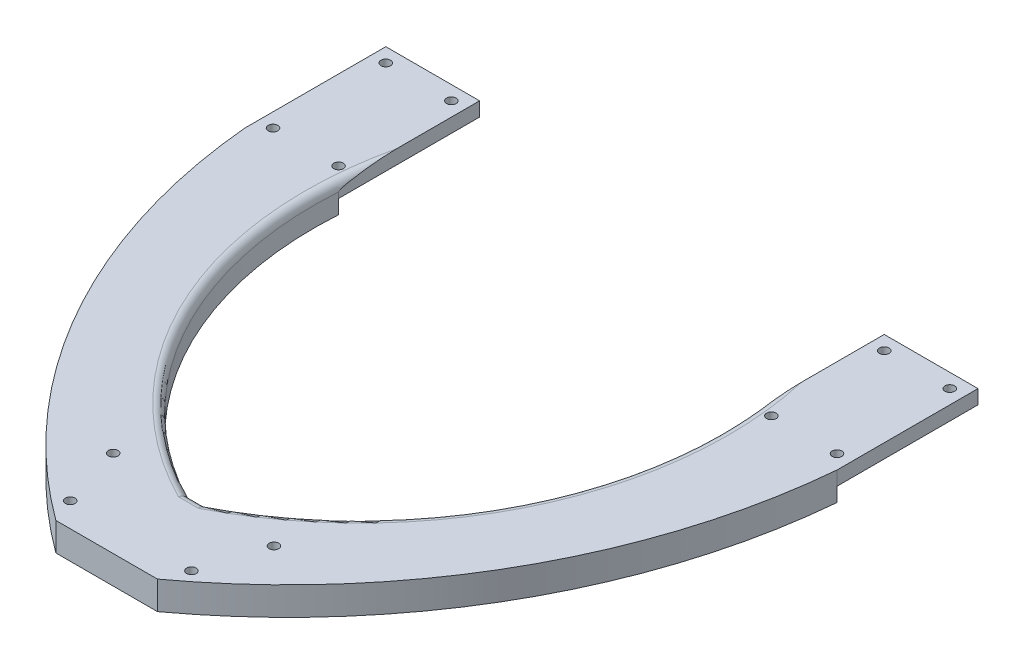
SolidWorks part; units mm, degrees
ref_plane "Ebene vorne" through (0, 0, 0) normal (0, 0, 1) x (1, 0, 0)
ref_plane "Ebene oben" through (0, 0, 0) normal (0, 1, 0) x (1, 0, 0)
ref_plane "Ebene rechts" through (0, 0, 0) normal (1, 0, 0) x (0, 0, -1)
sketch "Skizze1" plane through (0, 0, 0) normal (0, 1, 0) x (1, 0, 0)
  line L1 (-105, -210) -> (105, -210)
  line L2 (-105, -210) -> (-105, 210)
  line L3 (-105, 210) -> (105, 210)
  line L4 (105, -210) -> (105, 210)
  line L5 (-105, -210) -> (105, 210) construction
  line L6 (-105, 210) -> (105, -210) construction
  point P0 (0, 0)
  dimension "D1" = 210
  dimension "D2" = 420
extrude "Aufsatz-Linear austragen1" add sketch "Skizze1" along normal blind 10
ref_plane "Ebene1" through (0, -97.5366, 81.8429) normal (0, -0.766, 0.6428) x (1, 0, 0)
sketch "Skizze2" plane through (0, -97.5366, 81.8429) normal (0, -0.766, 0.6428) x (1, 0, 0)
  line L1 (-105, 167.2972) -> (105, 167.2972) construction
  circle A0 centre (0, 147.2972) radius 5
  dimension "D1" = 10
  dimension "D2" = 20
extrude "Schnitt-Linear austragen1" [suppressed] cut sketch "Skizze2" against normal blind 30 and the other way blind 10
sketch "Skizze3" [suppressed] plane through (0, -67.9923, 57.0523) normal (0, -0.766, 0.6428) x (1, 0, 0)
  circle A0 centre (0, 101.3345) radius 5
  dimension "D1" = 10
extrude "Aufsatz-Linear austragen2" [suppressed] add sketch "Skizze3" along normal blind 0.1
sketch "Skizze4" plane through (0, -97.5366, 81.8429) normal (0, -0.766, 0.6428) x (1, 0, 0)
  line L0 (0, 167.2972) -> (0, 159.9002) construction
  line L1 (-105, 167.2972) -> (105, 167.2972) construction
  line L2 (-25, 167.2972) -> (-25, 202.2972)
  line L3 (-25, 202.2972) -> (25, 202.2972)
  line L4 (-25, 167.2972) -> (25, 167.2972)
  line L5 (25, 167.2972) -> (25, 202.2972)
  point P10 (0, 202.2972)
  dimension "D1" = 50
  dimension "D2" = 35
extrude "Aufsatz-Linear austragen3" [suppressed] add sketch "Skizze4" against normal blind 10 separate body
sketch "Skizze5" plane through (0, 10, 0) normal (0, 1, 0) x (1, 0, 0)
  line L0 (0, 0) -> (0, -210) construction
  line L1 (-105, -210) -> (105, -210) construction
  line L2 (105, -210) -> (18, -210)
  line L3 (-18, -210) -> (-105, -56)
  line L4 (-105, 210) -> (-105, -210) construction
  line L5 (-105, -56) -> (-105, -210)
  line L6 (-105, -210) -> (-18, -210)
  line L7 (105, -56) -> (105, -210)
  line L8 (18, -210) -> (105, -56)
  line L9 (-105, 210) -> (-105, 125)
  line L10 (-105, 125) -> (105, 125)
  line L11 (105, -210) -> (105, 210) construction
  line L12 (105, 125) -> (105, 210)
  line L13 (105, 210) -> (-105, 210)
  line L14 (71.7468, -56) -> (-71.7468, -56)
  line L15 (-71.7468, -56) -> (-2.8247, -178)
  line L16 (71.7468, -56) -> (2.8247, -178)
  line L17 (-2.8247, -178) -> (2.8247, -178)
  line L18 (2.8247, -178) -> (0, -183) construction
  line L19 (-2.8247, -178) -> (0, -183) construction
  point P27 (0, -56)
  dimension "D1" = 36
  dimension "D2" = 154
  dimension "D3" = 85
  dimension "D4" = 32
  dimension "D5" = 27
extrude "Schnitt-Linear austragen2" cut sketch "Skizze5" against normal blind 10
sketch "Skizze6" plane through (0, 10, 0) normal (0, 1, 0) x (1, 0, 0)
  line L0 (0, -210) -> (0, -178) construction
  line L1 (-18, -210) -> (18, -210) construction
  line L2 (-2.8247, -178) -> (2.8247, -178) construction
  line L3 (0, -196.59) -> (-21.075, -196.59) construction
  circle A0 centre (-11, -205) radius 1.7
  circle A1 centre (-11, -188.18) radius 1.7
  circle A2 centre (11, -205) radius 1.7
  circle A3 centre (11, -188.18) radius 1.7
  dimension "D1" = 3.4
  dimension "D2" = 11
  dimension "D3" = 5
  dimension "D4" = 13.41
extrude "Schnitt-Linear austragen3" [suppressed] cut sketch "Skizze6" against normal through all
sketch "Skizze7" [suppressed] plane through (0, 0, 0) normal (0, -1, 0) x (1, 0, 0)
  line L0 (-11, 205) -> (-11, 210) construction
  line L1 (-18, 210) -> (18, 210) construction
  line L2 (-11, 205) -> (-5.1092, 205) construction
  line L3 (-11, 208.4064) -> (-8.05, 206.7032)
  line L4 (-8.05, 206.7032) -> (-8.05, 203.2968)
  line L5 (-11, 201.5936) -> (-8.05, 203.2968)
  line L6 (-11, 201.5936) -> (-13.95, 203.2968)
  line L7 (-13.95, 206.7032) -> (-13.95, 203.2968)
  line L8 (-11, 208.4064) -> (-13.95, 206.7032)
  line L9 (0, 210) -> (0, 121.6034) construction
  line L10 (11, 205) -> (11, 188.18) construction
  line L11 (11, 196.59) -> (0, 196.59) construction
  line L12 (11, 208.4064) -> (8.05, 206.7032)
  line L13 (11, 201.5936) -> (8.05, 203.2968)
  line L14 (8.05, 206.7032) -> (8.05, 203.2968)
  line L15 (11, 201.5936) -> (13.95, 203.2968)
  line L16 (13.95, 206.7032) -> (13.95, 203.2968)
  line L17 (11, 208.4064) -> (13.95, 206.7032)
  line L18 (-8.05, 186.4768) -> (-8.05, 189.8832)
  line L19 (-11, 191.5864) -> (-13.95, 189.8832)
  line L20 (-11, 191.5864) -> (-8.05, 189.8832)
  line L21 (-13.95, 186.4768) -> (-13.95, 189.8832)
  line L22 (-11, 184.7736) -> (-13.95, 186.4768)
  line L23 (-11, 184.7736) -> (-8.05, 186.4768)
  line L24 (8.05, 186.4768) -> (8.05, 189.8832)
  line L25 (11, 191.5864) -> (8.05, 189.8832)
  line L26 (11, 191.5864) -> (13.95, 189.8832)
  line L27 (13.95, 186.4768) -> (13.95, 189.8832)
  line L28 (11, 184.7736) -> (13.95, 186.4768)
  line L29 (11, 184.7736) -> (8.05, 186.4768)
  point P10 (-8.05, 205)
  dimension "D1" = 120
  dimension "D2" = 5.9
extrude "Schnitt-Linear austragen4" [suppressed] cut sketch "Skizze7" against normal blind 4
sketch "Skizze8" plane through (0, 10, 0) normal (0, 1, 0) x (1, 0, 0)
  line L0 (105, 115.41) -> (78.872, 115.41) construction
  line L1 (105, -56) -> (105, 125) construction
  line L2 (-105, 125) -> (105, 125) construction
  dimension "D1" = 9.59
ref_plane "Ebene2" through (0, 62.6966, -52.6087) normal (0, 0.766, -0.6428) x (-1, 0, 0)
sketch "Skizze9" plane through (0, 62.6966, -52.6087) normal (0, 0.766, -0.6428) x (-1, 0, 0)
  line L0 (-105, -81.9813) -> (-78.872, -81.9813) construction
  line L1 (-105, 49.3264) -> (-105, -89.3277) construction
  line L2 (0, -45.2589) -> (0, -16.2619) construction
  circle A0 centre (-100, -81.9813) radius 1.7
  circle A1 centre (100, -81.9813) radius 1.7
  circle A2 centre (-30, -81.9813) radius 1.7
  circle A3 centre (30, -81.9813) radius 1.7
  dimension "D1" = 3.4
  dimension "D2" = 5
  dimension "D3" = 30
extrude "Schnitt-Linear austragen5" [suppressed] cut sketch "Skizze9" against normal through all and the other way through all
ref_plane "Ebene3" through (0, 55.0361, -46.1808) normal (0, 0.766, -0.6428) x (-1, 0, 0)
sketch "Skizze10" [suppressed] plane through (0, 55.0361, -46.1808) normal (0, 0.766, -0.6428) x (-1, 0, 0)
  line L0 (-95, -81.9813) -> (-100, -81.9813) construction
  line L1 (-95, -81.9813) -> (-95, -30.0694) construction
  line L2 (-95, -78.7482) -> (-97.8, -80.3647)
  line L3 (-97.8, -80.3647) -> (-97.8, -83.5979)
  line L4 (-95, -85.2145) -> (-97.8, -83.5979)
  line L5 (-95, -85.2145) -> (-92.2, -83.5979)
  line L6 (-92.2, -80.3647) -> (-92.2, -83.5979)
  line L7 (-95, -78.7482) -> (-92.2, -80.3647)
  line L8 (0, 0) -> (0, -45.6283) construction
  line L9 (-30, -81.9813) -> (-95, -81.9813) construction
  line L10 (-62.5, -81.9813) -> (-62.5, -23.1343) construction
  line L11 (-32.8, -80.3647) -> (-32.8, -83.5979)
  line L12 (-30, -85.2145) -> (-32.8, -83.5979)
  line L13 (-30, -85.2145) -> (-27.2, -83.5979)
  line L14 (-27.2, -80.3647) -> (-27.2, -83.5979)
  line L15 (-30, -78.7482) -> (-27.2, -80.3647)
  line L16 (-30, -78.7482) -> (-32.8, -80.3647)
  line L17 (95, -78.7482) -> (92.2, -80.3647)
  line L18 (92.2, -80.3647) -> (92.2, -83.5979)
  line L19 (95, -85.2145) -> (92.2, -83.5979)
  line L20 (95, -85.2145) -> (97.8, -83.5979)
  line L21 (97.8, -80.3647) -> (97.8, -83.5979)
  line L22 (95, -78.7482) -> (97.8, -80.3647)
  line L23 (30, -78.7482) -> (32.8, -80.3647)
  line L24 (30, -78.7482) -> (27.2, -80.3647)
  line L25 (27.2, -80.3647) -> (27.2, -83.5979)
  line L26 (30, -85.2145) -> (27.2, -83.5979)
  line L27 (30, -85.2145) -> (32.8, -83.5979)
  line L28 (32.8, -80.3647) -> (32.8, -83.5979)
  point P9 (-97.8, -81.9813)
  point P31 (97.8, -81.9813)
  dimension "D1" = 120
  dimension "D2" = 5.6
extrude "Schnitt-Linear austragen6" [suppressed] cut sketch "Skizze10" against normal blind 10 and the other way blind 5
sketch "Skizze13" plane through (0, 10, 0) normal (0, 1, 0) x (1, 0, 0)
  line L0 (71.7468, -56) -> (105, -56) construction
  line L1 (71.7468, -56) -> (96.9548, -70.2409) construction
  line L2 (105, -56) -> (18, -210) construction
  line L3 (0, 0) -> (0, -38.1435) construction
  line L4 (2.8247, -178) -> (71.7468, -56) construction
  line L5 (84.3508, -63.1205) -> (108.762, -19.9098) construction
  line L6 (105, -56) -> (105, 125) construction
  line L7 (88.3734, -56) -> (88.3734, -1) construction
  line L8 (99, -58.9512) -> (105.7595, -46.9862) construction
  line L9 (87.7845, -86.4734) -> (62.5765, -72.2325) construction
  line L10 (77.1638, -80.4734) -> (91.1741, -80.4734) construction
  circle A0 centre (99, -58.9512) radius 1.7
  circle A1 centre (76.9708, -58.9512) radius 1.7
  circle A2 centre (86.8414, -80.4734) radius 1.7
  circle A3 centre (-86.8414, -80.4734) radius 1.7
  circle A4 centre (-99, -58.9512) radius 1.7
  circle A5 centre (-76.9708, -58.9512) radius 1.7
  dimension "D1" = 6
  dimension "D5" = 35
  dimension "D3" = 3.4
  dimension "D6" = 3.4
  dimension "D2" = 6
  dimension "D4" = 6
extrude "Schnitt-Linear austragen7" [suppressed] cut sketch "Skizze13" against normal through all
sketch "Skizze14" plane through (103.579, 0, 58.5154) normal (0.8707, 0, 0.4919) x (0.4919, 0, -0.8707)
  line L0 (-32.111, 5) -> (-32.111, 10)
  line L5 (2.889, 0) -> (2.889, 10) construction
  line L6 (-32.111, 5) -> (2.889, 5)
  line L7 (2.889, 10) -> (-173.9866, 10) construction
  line L8 (-32.111, 10) -> (2.889, 10)
  line L9 (2.889, 10) -> (2.889, 5)
  dimension "D1" = 35
extrude "Schnitt-Linear austragen8" [suppressed] cut sketch "Skizze14" against normal up to surface (28.9525 mm away) up to face at (37.2857, 5, 117)
mirror "Spiegeln1" [suppressed] about plane through (0, 0, 0) normal (1, 0, 0)
sketch "Skizze15" [suppressed] plane through (95, 0, 0) normal (1, 0, 0) x (0, 0, -1)
  line L0 (4, 10) -> (4, 0)
  line L1 (4, 0) -> (65, 0)
  line L2 (65, 0) -> (65, 10)
  line L3 (65, 10) -> (4, 10)
extrude "Schnitt-Linear austragen9" [suppressed] cut sketch "Skizze15" against normal through all
sketch "Skizze16" [suppressed] plane through (0, 0, 0) normal (0, -1, 0) x (1, 0, 0)
  line L0 (0, 210) -> (0, 178) construction
  line L1 (-18, 210) -> (18, 210) construction
  line L2 (-2.8247, 178) -> (2.8247, 178) construction
  line L3 (11, 196.59) -> (0, 196.59) construction
  line L4 (11, 205) -> (11, 188.18) construction
  line L6 (-17.5, 193.09) -> (17.5, 193.09)
  line L7 (-17.5, 193.09) -> (-17.5, 200.09)
  line L8 (-17.5, 200.09) -> (17.5, 200.09)
  line L9 (17.5, 193.09) -> (17.5, 200.09)
  line L10 (-17.5, 193.09) -> (17.5, 200.09) construction
  line L11 (-17.5, 200.09) -> (17.5, 193.09) construction
  dimension "D1" = 7
  dimension "D2" = 35
extrude "Schnitt-Linear austragen10" [suppressed] cut sketch "Skizze16" against normal blind 5
sketch "Skizze17" [suppressed] plane through (17.5, 0, 0) normal (-1, 0, 0) x (0, 0, 1)
  line L0 (196.59, 0) -> (196.59, 11.1261) construction
  line L1 (193.09, 0) -> (200.09, 0) construction
  line L2 (193.09, 5) -> (196.59, 8.5)
  line L3 (196.59, 8.5) -> (200.09, 5)
  line L4 (200.09, 5) -> (193.09, 5)
  dimension "D1" = 90
extrude "Schnitt-Linear austragen11" [suppressed] cut sketch "Skizze17" along normal up to surface (35 mm away)
sketch "Skizze18" [suppressed] plane through (0, 10, 0) normal (0, 1, 0) x (1, 0, 0)
  line L0 (0, -210) -> (0, 0) construction
  line L1 (-18, -210) -> (18, -210) construction
  line L2 (62.5765, -72.2325) -> (35.4483, -67.5372)
  line L3 (15.3378, -155.8503) -> (-22.1774, -134.6566)
  line L4 (2.8247, -178) -> (62.5765, -72.2325) construction
  line L5 (-15.3378, -155.8503) -> (22.1774, -134.6566)
  line L6 (58.6594, -79.166) -> (40.7308, -76.063)
  line L7 (0, -147.1854) -> (19.5429, -147.1854) construction
  line L8 (0, -95.4) -> (31.4297, -95.4) construction
  line L9 (11.6488, -162.3803) -> (0, -155.7995)
  line L10 (-71.7468, -56) -> (-2.8247, -178) construction
  line L11 (0, -95.4) -> (-37.5153, -116.5937) construction
  line L12 (-37.5153, -116.5937) -> (-39.2566, -117.5774) construction
  line L13 (-11.6488, -162.3803) -> (0, -155.7995)
  line L14 (-58.6594, -79.166) -> (-40.7308, -76.063)
  line L15 (-62.5765, -72.2325) -> (-35.4483, -67.5372)
  circle A0 centre (0, -95.4) radius 33.5
  arc A1 (7.4594, -151.3994) -> (7.4594, -142.9713) centre (9.84, -147.1854) cw
  arc A2 (-7.4594, -151.3994) -> (-7.4594, -142.9713) centre (-9.84, -147.1854) ccw
  circle A3 centre (0, -95.4) radius 45.0879
  point P17 (0, -147.1854)
  point P36 (5, -147.1854)
  point P40 (-5, -147.1854)
  line M16 (62.5765, -72.2325) -> (2.8247, -178)
  line M18 (-2.8247, -178) -> (-71.7468, -56)
  dimension "D2" = 67
  dimension "D5" = 2
  dimension "D4" = 10
  dimension "D1" = 114.6
  dimension "D3" = 7.5
  dimension "D6" = 7.5
extrude "Aufsatz-Linear austragen4" [suppressed] add sketch "Skizze18" against normal blind 10 contours A3 L15 L14 M18 | A3 A0 M16 M18 | A3 L6 L2 M16 | A2 L5 L3 | A3 L3 L5 | L3 A1 L5 | L13 L9 L3 L5 M18 M16
sketch "Skizze19" [suppressed] plane through (0, 0, 0) normal (0, -1, 0) x (1, 0, 0)
  circle A0 centre (0, 35.4) radius 31.5
  circle A1 centre (0, 35.4) radius 33.5
  circle A2 centre (0, 35.4) radius 33.5 construction
  dimension "D1" = 63
extrude "Aufsatz-Linear austragen5" [suppressed] add sketch "Skizze19" against normal blind 1
sketch "Skizze20" plane through (0, 10, 0) normal (0, 1, 0) x (1, 0, 0)
  line L0 (105, 119.52) -> (55.4083, 119.52) construction
  line L1 (105, -56) -> (105, 125) construction
  line L2 (-105, 125) -> (105, 125) construction
  line L3 (0, 125) -> (0, 96.9732) construction
  line L4 (105, 43.82) -> (35.5869, 43.82) construction
  circle A0 centre (96, 119.52) radius 1.7
  circle A1 centre (54, 119.52) radius 1.7
  circle A2 centre (-54, 119.52) radius 1.7
  circle A3 centre (-96, 119.52) radius 1.7
  circle A4 centre (92.5, 43.82) radius 1.7
  circle A5 centre (57.5, 43.82) radius 1.7
  circle A6 centre (-92.5, 43.82) radius 1.7
  circle A7 centre (-57.5, 43.82) radius 1.7
  dimension "D1" = 3.4
  dimension "D2" = 5.48
  dimension "D3" = 9
  dimension "D4" = 42
  dimension "D5" = 75.7
  dimension "D6" = 12.5
  dimension "D7" = 35
extrude "Schnitt-Linear austragen12" cut sketch "Skizze20" against normal through all
sketch "Skizze21" plane through (0, 10, 0) normal (0, 1, 0) x (1, 0, 0)
  line L0 (-71.7468, -56) -> (-71.7468, 19)
  line L1 (-71.7468, 19) -> (71.7468, 19)
  line L2 (71.7468, 19) -> (71.7468, -56)
  line L3 (71.7468, -56) -> (-71.7468, -56) construction
  line L4 (-71.7468, -56) -> (71.7468, -56)
  dimension "D1" = 75
extrude "Schnitt-Linear austragen13" cut sketch "Skizze21" against normal through all
sketch "Skizze22" plane through (0, 10, 0) normal (0, 1, 0) x (1, 0, 0)
  line L0 (-71.7468, -56) -> (-2.8247, -178)
  arc A0 (-71.7468, -56) -> (-2.8247, -178) centre (55.7113, -64.4627) ccw
  line M19 (-2.8247, -178) -> (-71.7468, -56)
extrude "Schnitt-Linear austragen14" cut sketch "Skizze22" against normal through all contours M19 region at (-44.6278, 10, 121.1478)
sketch "Skizze23" plane through (0, 10, 0) normal (0, 1, 0) x (1, 0, 0)
  line L0 (-18, -210) -> (-105, -56) construction
  line L1 (-105, -56) -> (-18, -210)
  arc A0 (-18, -210) -> (-105, -56) centre (108.9155, -36.7263) cw
  arc A2 (-71.7468, -56) -> (-2.8247, -178) centre (55.7113, -64.4627) ccw construction
  dimension "D1" = 60
extrude "Aufsatz-Linear austragen6" add sketch "Skizze23" against normal blind 10
mirror "Spiegeln2" about plane through (0, 0, 0) normal (1, 0, 0) of "Aufsatz-Linear austragen6", "Schnitt-Linear austragen14"
sketch "Skizze25" plane through (0, 10, 0) normal (0, 1, 0) x (1, 0, 0)
  line L0 (-105, -56) -> (-71.7468, -56) construction
  line L1 (-105, -6) -> (-105, -56) construction
  line L2 (-105, -6) -> (-71.7468, -6) construction
  line L3 (-71.7468, 19) -> (-71.7468, -56) construction
  line L4 (-88.3734, -6) -> (-88.3734, -56) construction
  line L5 (-105, -31) -> (-71.7468, -31) construction
  line L6 (-105, 125) -> (-105, -56) construction
  circle A0 centre (-100, -11) radius 1.7
  circle A1 centre (-76.7468, -11) radius 1.7
  circle A2 centre (-76.7468, -51) radius 1.7
  circle A3 centre (-100, -51) radius 1.7
  dimension "D2" = 3.4
  dimension "D1" = 50
  dimension "D3" = 5
  dimension "D4" = 5
extrude "Schnitt-Linear austragen15" cut sketch "Skizze25" against normal through all
sketch "Skizze26" plane through (-105, 0, 0) normal (-1, 0, 0) x (0, 0, 1)
  line L0 (56, 5) -> (56, 0)
  line L1 (56, 0) -> (56, 10) construction
  line L2 (56, 5) -> (6, 5)
  line L3 (6, 5) -> (6, 10)
  line L4 (-125, 0) -> (56, 0) construction
  line L5 (5.0128, 19.5087) -> (6, 10)
  line L6 (5.0128, 19.5087) -> (-137.7077, 19.5087)
  line L7 (-137.7077, 19.5087) -> (-137.7077, -14.4017)
  line L8 (-137.7077, -14.4017) -> (4.1968, -14.4017)
  line L9 (4.1968, -14.4017) -> (56, 0)
  line L10 (-125, 10) -> (56, 10) construction
mirror "Spiegeln3" about plane through (0, 0, 0) normal (1, 0, 0) of "Schnitt-Linear austragen15"
extrude "Schnitt-Linear austragen16" cut sketch "Skizze26" against normal through all
fillet "Verrundung1" radius 3 3 edges at (55.5067, 10, 127.2937) (-55.5067, 10, 127.2937) (0, 10, 178)
sketch "Skizze27" plane through (0, 10, 0) normal (0, 1, 0) x (1, 0, 0)
  line L0 (0, -210) -> (0, -164.5001) construction
  line L1 (-18, -210) -> (18, -210) construction
  line L2 (17.5, -210) -> (17.5, -183.18) construction
  line L3 (-17.5, -210) -> (-17.5, -183.18) construction
  line L4 (17.5, -210) -> (32.5, -197.4135) construction
  line L5 (-17.5, -183.18) -> (17.5, -183.18) construction
  line L6 (17.5, -183.18) -> (32.5, -170.5935) construction
  line L7 (32.5, -170.5935) -> (32.5, -197.4135) construction
  line L8 (-17.5, -210) -> (-32.5, -197.4135) construction
  line L9 (-32.5, -170.5935) -> (-32.5, -197.4135) construction
  line L10 (-17.5, -183.18) -> (-32.5, -170.5935) construction
  line L11 (28.5, -179.1715) -> (32.5, -179.1715) construction
  line L12 (28.5, -179.1715) -> (25.9288, -176.1074) construction
  line L13 (21.5, -201.422) -> (24.0712, -204.4862) construction
  line L14 (21.5, -201.422) -> (17.5, -201.422) construction
  circle A0 centre (28.5, -179.1715) radius 1.7
  circle A1 centre (21.5, -201.422) radius 1.7
  circle A2 centre (-21.5, -201.422) radius 1.7
  circle A3 centre (-28.5, -179.1715) radius 1.7
  dimension "D5" = 3.4
  dimension "D1" = 17.5
  dimension "D2" = 140
  dimension "D3" = 26.82
  dimension "D4" = 15
  dimension "D6" = 4
  dimension "D7" = 4
extrude "Schnitt-Linear austragen17" cut sketch "Skizze27" against normal through all
sketch "Skizze28" plane through (0, 0, 0) normal (0, -1, 0) x (1, 0, 0)
  line L0 (21.5, 201.422) -> (21.5, 205.9223) construction
  line L1 (21.5, 201.422) -> (27.5804, 201.422) construction
  line L2 (21.5, 204.8283) -> (24.45, 203.1252)
  line L3 (24.45, 203.1252) -> (24.45, 199.7188)
  line L4 (21.5, 198.0156) -> (24.45, 199.7188)
  line L5 (21.5, 198.0156) -> (18.55, 199.7188)
  line L6 (18.55, 203.1252) -> (18.55, 199.7188)
  line L7 (21.5, 204.8283) -> (18.55, 203.1252)
  line L8 (28.5, 179.1715) -> (28.5, 188.5672) construction
  line L9 (28.5, 179.1715) -> (36.4607, 179.1715) construction
  line L10 (28.5, 182.5779) -> (31.45, 180.8747)
  line L11 (31.45, 180.8747) -> (31.45, 177.4683)
  line L12 (28.5, 175.7652) -> (31.45, 177.4683)
  line L13 (28.5, 175.7652) -> (25.55, 177.4683)
  line L14 (25.55, 180.8747) -> (25.55, 177.4683)
  line L15 (28.5, 182.5779) -> (25.55, 180.8747)
  line L16 (0, 210) -> (0, 191.8778) construction
  line L17 (-18, 210) -> (18, 210) construction
  line L18 (-28.5, 182.5779) -> (-25.55, 180.8747)
  line L19 (-25.55, 180.8747) -> (-25.55, 177.4683)
  line L20 (-28.5, 175.7652) -> (-25.55, 177.4683)
  line L21 (-28.5, 175.7652) -> (-31.45, 177.4683)
  line L22 (-31.45, 180.8747) -> (-31.45, 177.4683)
  line L23 (-28.5, 182.5779) -> (-31.45, 180.8747)
  line L24 (-21.5, 201.422) -> (-21.5, 205.9223) construction
  line L25 (-21.5, 204.8283) -> (-18.55, 203.1252)
  line L26 (-18.55, 203.1252) -> (-18.55, 199.7188)
  line L27 (-21.5, 198.0156) -> (-18.55, 199.7188)
  line L28 (-21.5, 198.0156) -> (-24.45, 199.7188)
  line L29 (-24.45, 203.1252) -> (-24.45, 199.7188)
  line L30 (-21.5, 204.8283) -> (-24.45, 203.1252)
  point P9 (24.45, 201.422)
  point P12 (18.55, 201.422)
  point P22 (31.45, 179.1715)
  point P35 (-31.45, 179.1715)
  point P44 (-18.55, 201.422)
  point P45 (-24.45, 201.422)
  dimension "D1" = 120
  dimension "D2" = 5.9
  dimension "D3" = 5.9
  dimension "D4" = 120
extrude "Schnitt-Linear austragen18" cut sketch "Skizze28" against normal blind 5
